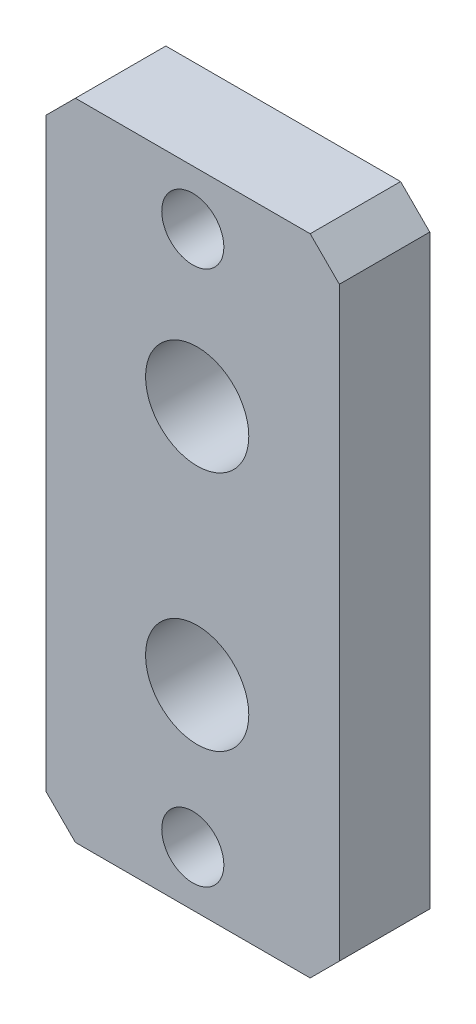
SolidWorks part; units mm, degrees
material "PET"
ref_plane "Front Plane" through (0, 0, 0) normal (0, 0, 1) x (1, 0, 0)
ref_plane "Top Plane" through (0, 0, 0) normal (0, 1, 0) x (1, 0, 0)
ref_plane "Right Plane" through (0, 0, 0) normal (1, 0, 0) x (0, 0, -1)
sketch "Sketch1" plane through (0, 0, 0) normal (0, 0, 1) x (1, 0, 0)
  line L1 (-9.0499, 33.1157) -> (-9.0499, 50.6417)
  line L2 (-9.5579, 51.1497) -> (-19.7814, 51.1497)
  line L3 (-20.2894, 50.6417) -> (-20.2894, 33.1157)
  line L4 (-19.7814, 32.6077) -> (-9.5579, 32.6077)
  line L5 (-9.3039, 33.1157) -> (-9.3039, 50.6417)
  line L6 (-9.5579, 50.8957) -> (-19.7814, 50.8957)
  line L7 (-20.0354, 50.6417) -> (-20.0354, 33.1157)
  line L8 (-19.7814, 32.8617) -> (-9.5579, 32.8617)
  line L9 (-9.3039, 33.1157) -> (-9.3039, 50.6417) construction
  line L10 (-9.5579, 50.8957) -> (-19.7814, 50.8957) construction
  line L11 (-20.0354, 50.6417) -> (-20.0354, 33.1157) construction
  line L12 (-19.7814, 32.8617) -> (-9.5579, 32.8617) construction
  line L16 (-9.0499, 41.8787) -> (-20.2894, 41.8787) construction
  line L18 (-21.0514, 27.8452) -> (-8.2879, 27.8452)
  line L19 (-21.0514, 27.8452) -> (-21.0514, 55.9122)
  line L20 (-21.0514, 55.9122) -> (-8.2879, 55.9122)
  line L21 (-8.2879, 27.8452) -> (-8.2879, 55.9122)
  line L22 (-21.0514, 27.8452) -> (-8.2879, 55.9122) construction
  line L23 (-21.0514, 55.9122) -> (-8.2879, 27.8452) construction
  arc A0 (-9.0499, 50.6417) -> (-9.5579, 51.1497) centre (-9.5579, 50.6417) ccw
  arc A1 (-19.7814, 51.1497) -> (-20.2894, 50.6417) centre (-19.7814, 50.6417) ccw
  arc A2 (-20.2894, 33.1157) -> (-19.7814, 32.6077) centre (-19.7814, 33.1157) ccw
  arc A3 (-9.5579, 32.6077) -> (-9.0499, 33.1157) centre (-9.5579, 33.1157) ccw
  arc A4 (-9.3039, 50.6417) -> (-9.5579, 50.8957) centre (-9.5579, 50.6417) ccw
  arc A5 (-19.7814, 50.8957) -> (-20.0354, 50.6417) centre (-19.7814, 50.6417) ccw
  arc A6 (-20.0354, 33.1157) -> (-19.7814, 32.8617) centre (-19.7814, 33.1157) ccw
  arc A7 (-9.5579, 32.8617) -> (-9.3039, 33.1157) centre (-9.5579, 33.1157) ccw
  arc A8 (-9.3039, 50.6417) -> (-9.5579, 50.8957) centre (-9.5579, 50.6417) ccw construction
  arc A9 (-19.7814, 50.8957) -> (-20.0354, 50.6417) centre (-19.7814, 50.6417) ccw construction
  arc A10 (-20.0354, 33.1157) -> (-19.7814, 32.8617) centre (-19.7814, 33.1157) ccw construction
  arc A11 (-9.5579, 32.8617) -> (-9.3039, 33.1157) centre (-9.5579, 33.1157) ccw construction
  point P26 (-14.6696, 41.8787)
  dimension "D3" = 0.762
  dimension "D4" = 4.7625
  dimension "D1" = 0
  dimension "D2" = 0.254
extrude "Boss-Extrude1" add sketch "Sketch1" against normal blind 0.762
sketch "Sketch3" plane through (0, 0, 0) normal (0, 0, 1) x (1, 0, 0)
  line L4 (-8.2879, 27.8452) -> (-8.2879, 55.9122)
  line L5 (-8.2879, 55.9122) -> (-21.0514, 55.9122)
  line L6 (-21.0514, 55.9122) -> (-21.0514, 27.8452)
  line L7 (-21.0514, 27.8452) -> (-8.2879, 27.8452)
  line L8 (-8.2879, 27.8452) -> (-8.2879, 55.9122)
  line L9 (-8.2879, 55.9122) -> (-21.0514, 55.9122)
  line L10 (-21.0514, 55.9122) -> (-21.0514, 27.8452)
  line L11 (-21.0514, 27.8452) -> (-8.2879, 27.8452)
  dimension "D1" = 0
extrude "Boss-Extrude2" add sketch "Sketch3" along normal blind 3.175
hole_wizard "CSK for #2 Flat Head Machine Screw (100)1" positions "Sketch6" profile "Sketch5" countersink size "#2" standard "ANSI Inch" end condition up to next
sketch "Sketch6" plane through (0, 0, -0.762) normal (0, 0, -1) x (-1, 0, 0)
  line L0 (14.6696, 27.8452) -> (14.6696, 32.6077) construction
  line L1 (21.0514, 27.8452) -> (8.2879, 27.8452) construction
  line L2 (19.7814, 32.6077) -> (9.5579, 32.6077) construction
  line L3 (8.2879, 41.8787) -> (21.0514, 41.8787) construction
  line L4 (8.2879, 27.8452) -> (8.2879, 55.9122) construction
  line L5 (21.0514, 55.9122) -> (21.0514, 27.8452) construction
  point P8 (14.6696, 30.2264)
  point P20 (14.6696, 53.5309)
sketch "Sketch5" plane through (-14.6696, 53.5309, -0.762) normal (1, 0, 0) x (0, 1, 0)
  line L0 (0, 0) -> (0, 3.937)
  line L1 (0, 3.937) -> (1.3525, 3.937)
  line L2 (1.3525, 3.937) -> (1.3525, 0.698)
  line L3 (1.3525, 0.698) -> (2.1844, 0)
  line L5 (2.1844, 0) -> (0, 0)
  line L6 (-1.3525, 0.698) -> (-2.1844, 0) construction
  line L11 (0, -6.35) -> (0, 107.95) construction
  dimension "Thru Hole Dia." = 2.7051
  dimension "Thru Hole Depth" = 3.937
  dimension "Near C'Sink Dia." = 4.3688
  dimension "Near C'Sink Angle" = 100
hole_wizard "#16 (0.177) Diameter Hole1" positions "Sketch7" profile "Sketch8" hole size "#16" standard "ANSI Inch" end condition up to next
sketch "Sketch7" plane through (0, 0, 0) normal (0, 0, -1) x (-1, 0, 0)
  point P0 (14.4791, 36.4361)
  point P3 (14.4791, 46.9403)
sketch "Sketch8" plane through (-14.4791, 36.4361, 0) normal (1, 0, 0) x (0, 1, 0)
  line L0 (0, 0) -> (0, 3.175)
  line L1 (0, 3.175) -> (2.2479, 3.175)
  line L2 (2.2479, 3.175) -> (2.2479, 0)
  line L5 (2.2479, 0) -> (0, 0)
  line L11 (0, -6.35) -> (0, 107.95) construction
  dimension "Thru Hole Dia." = 4.4958
  dimension "Thru Hole Depth" = 3.175
chamfer "Chamfer1" distance 1.27 angle 45 4 edges at (-21.0514, 55.9122, 1.2065) (-8.2879, 55.9122, 1.2065) (-21.0514, 27.8452, 1.2065) (-8.2879, 27.8452, 1.2065)
